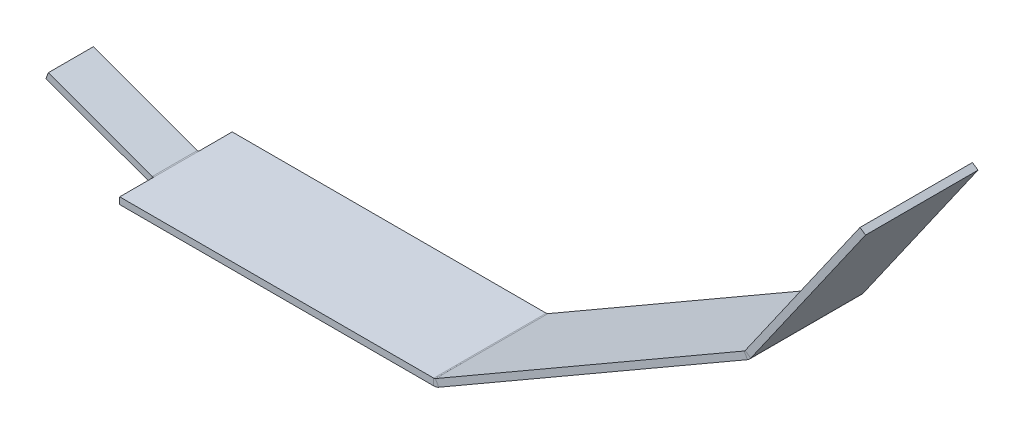
SolidWorks part; units mm, degrees
note: The reader was unsure of these and kept them because the rebuilt part matched: flange length of "Edge-Flange1", "Edge-Flange2", "Edge-Flange3".
ref_plane "Front Plane" through (0, 0, 0) normal (0, 0, 1) x (1, 0, 0)
ref_plane "Top Plane" through (0, 0, 0) normal (0, 1, 0) x (1, 0, 0)
ref_plane "Right Plane" through (0, 0, 0) normal (1, 0, 0) x (0, 0, -1)
sketch "Sketch1" plane through (0, 0, 0) normal (0, 1, 0) x (1, 0, 0)
  line L1 (-35, -12.5) -> (35, -12.5)
  line L2 (-35, -12.5) -> (-35, 12.5)
  line L3 (-35, 12.5) -> (35, 12.5)
  line L4 (35, -12.5) -> (35, 12.5)
  line L5 (-35, -12.5) -> (35, 12.5) construction
  line L6 (-35, 12.5) -> (35, -12.5) construction
  point P0 (0, 0)
  dimension "D1" = 70
  dimension "D2" = 25
base flange "Base-Flange1" sketch "Sketch1" thickness 1.5 reverse thickness direction no parameters "D1"=0.7366
ref_plane "Plane1" through (-35, -1.5, -12.5) normal (0, 0, 1) x (1, 0, 0)
edge flange "Edge-Flange1" sketch "Sketch13" flange angle 160 flange length 25 flange position bend outside bend radius 0.7366 thickness 1.5 relief rectangular parameters "D6"=10
sketch "Sketch13" plane through (-35, 0, 0) normal (-0.342, -0.9397, 0) x (0, 0, 1)
  line L2 (-5, 0) -> (-5, 24.7355)
  line L3 (-5, 24.7355) -> (5, 24.7355)
  line L4 (5, 24.7355) -> (5, 0)
  line L7 (-12.5, 0) -> (12.5, 0) construction
  line L8 (-5, 0) -> (5, 0)
  line L9 (-12.5, -65.7785) -> (-12.5, 0) construction
  point P4 (0, 0)
  point P5 (-9.1509, 0)
  point P7 (9.2504, 0)
  dimension "D1" = 10
  dimension "D2" = 7.5
bend "EdgeBend1" bend radius 0.7366 bend angle 20 parameters "D5"=1
edge flange "Edge-Flange2" sketch "Sketch18" flange angle 150 flange length 80 flange position material outside bend radius 0.7366 thickness 1.5 relief rectangular parameters "D6"=10
sketch "Sketch18" plane through (35, 0, 0) normal (0.5, -0.866, 0) x (0, 0, -1)
  line L0 (-12.5, 0) -> (12.5, 0) construction
  line L1 (-12.5, 0) -> (12.5, 0)
  line L2 (-12.5, 0) -> (-12.5, 79.5981)
  line L3 (-12.5, 79.5981) -> (12.5, 79.5981)
  line L4 (12.5, 79.5981) -> (12.5, 0)
bend "EdgeBend2" bend radius 0.7366 bend angle 30 parameters "D5"=2
edge flange "Edge-Flange3" sketch "Sketch21" flange angle 155 flange length 45 flange position material outside bend radius 0.7366 thickness 1.5 relief rectangular parameters "D6"=10
sketch "Sketch21" plane through (103.934, 39.799, 0) normal (0.8192, -0.5736, 0) x (0, 0, -1)
  line L0 (12.5, 0) -> (-12.5, 0) construction
  line L1 (12.5, 0) -> (-12.5, 0)
  line L2 (-12.5, 0) -> (-12.5, 44.6675)
  line L3 (-12.5, 44.6675) -> (12.5, 44.6675)
  line L4 (12.5, 44.6675) -> (12.5, 0)
bend "EdgeBend3" bend radius 0.7366 bend angle 25 parameters "D5"=3
sketch "Bend-Lines1" [suppressed] plane through (0, 0, 0) normal (0, 1, 0) x (1, 0, 0)
sketch "Bounding-Box1" [suppressed] plane through (0, 0, 0) normal (0, 1, 0) x (1, 0, 0)
sheet metal parameters "Sheet-Metal1" thickness 1.5 parameters "D1"=0.7366
flat pattern "Flat-Pattern1" [suppressed]
sketch "Bend-Lines2" plane through (0, 0, 0) normal (0, 1, 0) x (1, 0, 0)
sketch3d "Bounding-Box2" [suppressed]
  line L0 (35, 12.5, 0) -> (-35, 12.5, 0) construction
  line L1 (35, -12.5, 0) -> (-35, -12.5, 0) construction
  line L2 (35, 12.5, 0) -> (35, -12.5, 0) construction
  line L3 (-35, 12.5, 0) -> (-35, -12.5, 0) construction
sheet metal parameters "Sheet-Metal2" thickness 1.5 parameters "D1"=0.7366
flat pattern "Flat-Pattern1"
sketch "Bend-Lines2" plane through (0, 0, 0) normal (0, 1, 0) x (1, 0, 0)
  line L0 (-35.2595, 5) -> (-35.2595, -5) construction
  line L1 (-35.2595, 5) -> (-35.2595, -5) construction
sketch3d "Bounding-Box2" [suppressed]
  line L0 (35, 12.5, 0) -> (-60.1245, 12.5, 0) construction
  line L1 (35, -12.5, 0) -> (-60.1245, -12.5, 0) construction
  line L2 (35, 12.5, 0) -> (35, -12.5, 0) construction
  line L3 (-60.1245, 12.5, 0) -> (-60.1245, -12.5, 0) construction
bend of the flat pattern "Flatten-<EdgeBend1>1"
sheet metal parameters "Sheet-Metal3" thickness 1.5 parameters "D1"=0.7366
flat pattern "Flat-Pattern1"
sketch "Bend-Lines2" plane through (0, 0, 0) normal (0, 1, 0) x (1, 0, 0)
  line L0 (-35.2595, 5) -> (-35.2595, -5) construction
  line L1 (-35.2595, 5) -> (-35.2595, -5) construction
  line L2 (35.161, -12.5) -> (35.161, 12.5) construction
  line L3 (35.161, -12.5) -> (35.161, 12.5) construction
sketch3d "Bounding-Box2" [suppressed]
  line L0 (115.7261, 12.5, 0) -> (-60.1245, 12.5, 0) construction
  line L1 (115.7261, -12.5, 0) -> (-60.1245, -12.5, 0) construction
  line L2 (115.7261, 12.5, 0) -> (115.7261, -12.5, 0) construction
  line L3 (-60.1245, 12.5, 0) -> (-60.1245, -12.5, 0) construction
bend of the flat pattern "Flatten-<EdgeBend1>1"
bend of the flat pattern "Flatten-<EdgeBend2>1"
sheet metal parameters "Sheet-Metal4" thickness 1.5 parameters "D1"=0.7366
flat pattern "Flat-Pattern1"
sketch "Bend-Lines2" plane through (0, 0, 0) normal (0, 1, 0) x (1, 0, 0)
  line L0 (-35.2595, 5) -> (-35.2595, -5) construction
  line L1 (-35.2595, 5) -> (-35.2595, -5) construction
  line L2 (35.1918, -12.5) -> (35.1918, 12.5) construction
  line L3 (35.1918, -12.5) -> (35.1918, 12.5) construction
  line L4 (115.1427, -12.5) -> (115.1427, 12.5) construction
  line L5 (115.1427, -12.5) -> (115.1427, 12.5) construction
sketch3d "Bounding-Box2" [suppressed]
  line L0 (159.9712, 12.5, 0) -> (-60.1245, 12.5, 0) construction
  line L1 (159.9712, -12.5, 0) -> (-60.1245, -12.5, 0) construction
  line L2 (159.9712, 12.5, 0) -> (159.9712, -12.5, 0) construction
  line L3 (-60.1245, 12.5, 0) -> (-60.1245, -12.5, 0) construction
bend of the flat pattern "Flatten-<EdgeBend1>1"
bend of the flat pattern "Flatten-<EdgeBend2>1"
bend of the flat pattern "Flatten-<EdgeBend3>1"
